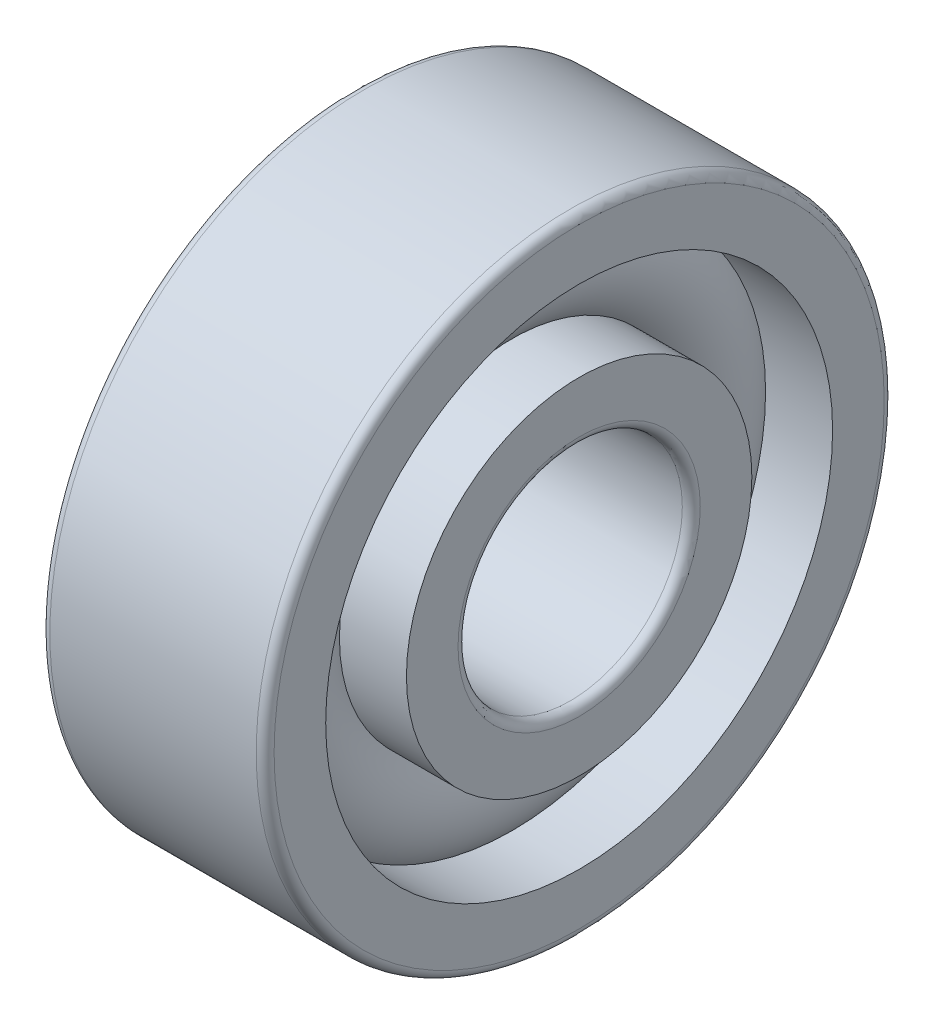
SolidWorks part; units mm, degrees
ref_plane "Plane1" through (0, 0, 0) normal (0, 0, 1) x (1, 0, 0)
ref_plane "Plane2" through (0, 0, 0) normal (0, 1, 0) x (1, 0, 0)
ref_plane "Plane3" through (0, 0, 0) normal (1, 0, 0) x (0, 0, -1)
sketch "Clipboard" plane through (0, 0, 0) normal (0, 0, 1) x (1, 0, 0)
  line L0 (-10, 0) -> (10, 0) construction
  line L1 (0, 0) -> (22.3471, -0.7804)
  line L2 (0, 0) -> (4.7471, 0.1658)
  line L3 (0, 0) -> (22.3471, -0.7804)
  line L4 (0, 0) -> (-22.3573, -0.3902)
  dimension "BallCLRad" = 4.75
sketch "CagSpiSke" plane through (0, 0, 0) normal (0, 0, 1) x (1, 0, 0)
  line L0 (0.135, 4.525) -> (0.135, 4.975)
  line L1 (0.135, 4.975) -> (-0.135, 4.975)
  line L2 (-0.135, 4.975) -> (-0.135, 4.525)
  line L3 (-0.135, 4.525) -> (0.135, 4.525)
  line L4 (-20.6375, 0) -> (20.6375, 0) construction
  line L5 (0, 0) -> (0, 23.7692) construction
  dimension "OD" = 9.95
  dimension "ID" = 9.05
revolve "CageSpine" add sketch "CagSpiSke" angle 0.001 about L4 reverse direction yes
ref_axis "Axis1" through (-50, 0, 0) along (1, 0, 0)
sketch "CagBalSke" plane through (0, 0, 0) normal (0, 0, 1) x (1, 0, 0)
  line L0 (-1.485, 4.75) -> (1.485, 4.75)
  line L1 (-1.905, 4.75) -> (1.905, 4.75) construction
  line L2 (-10, 0) -> (10, 0) construction
  line L3 (0, 0) -> (0, 24) construction
  arc A0 (1.485, 4.75) -> (-1.485, 4.75) centre (0, 4.75) cw
  dimension "BallCLRad" = 4.75
revolve "CageBall" [suppressed] add sketch "CagBalSke" angle 360 about L1 reverse direction yes
pattern_circular "CageBalls" [suppressed] count 2 every 180 about axis through (-50, 0, 0) along (1, 0, 0)
sketch "CagTrmODSke" plane through (0, 0, 0) normal (0, 0, 1) x (1, 0, 0)
  line L0 (1.486, 4.975) -> (1.486, 6.236)
  line L1 (1.486, 6.236) -> (-1.486, 6.236)
  line L2 (-1.486, 6.236) -> (-1.486, 4.975)
  line L3 (-1.486, 4.975) -> (1.486, 4.975)
  line L4 (-20.6375, 0) -> (20.6375, 0) construction
  line L5 (0, 0) -> (0, 25) construction
  dimension "Width" = 2.972
  dimension "ID" = 9.95
  dimension "OD" = 12.472
revolve "CageTrimOD" [suppressed] cut sketch "CagTrmODSke" angle 360 about L4 reverse direction yes
sketch "CagTrmIDSke" plane through (0, 0, 0) normal (0, 0, 1) x (1, 0, 0)
  line L0 (1.486, 3.266) -> (1.486, 4.525)
  line L1 (1.486, 4.525) -> (-1.486, 4.525)
  line L2 (-1.486, 4.525) -> (-1.486, 3.266)
  line L3 (-1.486, 3.266) -> (1.486, 3.266)
  line L4 (-20.6375, 0) -> (20.6375, 0) construction
  line L5 (0, 0) -> (0, 25) construction
  dimension "Width" = 2.972
  dimension "ID" = 6.532
  dimension "OD" = 9.05
revolve "CageTrimID" [suppressed] cut sketch "CagTrmIDSke" angle 360 about L4 reverse direction yes
sketch "BalSimSke" plane through (0, 0, 0) normal (0, 0, 1) x (1, 0, 0)
  line L0 (-10, 0) -> (10, 0) construction
  line L1 (-10, 4.75) -> (10, 4.75) construction
  line L2 (0, 0) -> (0, 23) construction
  circle A0 centre (0, 4.75) radius 1.35
  dimension "BallCLRad" = 4.75
  dimension "Ball_diameter" = 2.7
revolve "BallsSimplified" add sketch "BalSimSke" angle 360 about L0
sketch "BalDetSke" plane through (0, 0, 0) normal (0, 0, 1) x (1, 0, 0)
  line L0 (-1.35, 4.75) -> (1.35, 4.75)
  line L1 (-1.905, 4.75) -> (1.905, 4.75) construction
  line L2 (0, 0) -> (0, 25) construction
  arc A0 (1.35, 4.75) -> (-1.35, 4.75) centre (0, 4.75) cw
  dimension "BallCLRad" = 4.75
  dimension "Ball_diameter" = 2.7
revolve "BallDetailed" [suppressed] add sketch "BalDetSke" angle 360 about L1 reverse direction yes
sketch "InnRacSke" plane through (0, 0, 0) normal (0, 0, 1) x (1, 0, 0)
  line L0 (-0.9724, 3.85) -> (-2.5, 3.85)
  line L1 (-2.5, 3.85) -> (-2.5, 2.7)
  line L2 (-2.3, 2.5) -> (2.3, 2.5)
  line L3 (2.5, 2.7) -> (2.5, 3.85)
  line L4 (2.5, 3.85) -> (0.9724, 3.85)
  line L5 (-20.6375, 0) -> (20.6375, 0) construction
  line L6 (0, 0) -> (0, 30) construction
  arc A0 (-2.5, 2.7) -> (-2.3, 2.5) centre (-2.3, 2.7) ccw
  arc A1 (2.3, 2.5) -> (2.5, 2.7) centre (2.3, 2.7) ccw
  arc A2 (0.9724, 3.85) -> (-0.9724, 3.85) centre (0, 4.75) cw
  dimension "BallCLRad" = 4.75
  dimension "Fillet_radius" = 0.2
  dimension "Ball_diameter" = 2.65
  dimension "ID" = 5
  dimension "OD" = 7.7
  dimension "Width" = 5
revolve "InnerRace" add sketch "InnRacSke" angle 360 about L5 reverse direction yes
sketch "OutRacSke" plane through (0, 0, 0) normal (0, 0, 1) x (1, 0, 0)
  line L0 (-0.9724, 5.65) -> (-2.5, 5.65)
  line L1 (-2.5, 5.65) -> (-2.5, 6.8)
  line L2 (-2.3, 7) -> (2.3, 7)
  line L3 (2.5, 6.8) -> (2.5, 5.65)
  line L4 (2.5, 5.65) -> (0.9724, 5.65)
  line L5 (-20.6375, 0) -> (20.6375, 0) construction
  line L6 (0, 0) -> (0, 30) construction
  arc A0 (-2.5, 6.8) -> (-2.3, 7) centre (-2.3, 6.8) cw
  arc A1 (2.3, 7) -> (2.5, 6.8) centre (2.3, 6.8) cw
  arc A2 (0.9724, 5.65) -> (-0.9724, 5.65) centre (0, 4.75) ccw
  dimension "BallCLRad" = 4.75
  dimension "Fillet_radius" = 0.2
  dimension "Ball_diameter" = 2.65
  dimension "Width" = 5
revolve "OuterRace" add sketch "OutRacSke" angle 360 about L5 reverse direction yes
pattern_circular "BallsDetailed" [suppressed] count 2 every 180 about axis through (-50, 0, 0) along (1, 0, 0)
equation "\"BallCLRad@Clipboard\" = ( \"OD@OutRacSke\" + \"ID@InnRacSke\" ) / 4"
equation "\"BallCLRad@BalSimSke\" = \"BallCLRad@Clipboard\""
equation "\"BallCLRad@BalDetSke\" = \"BallCLRad@Clipboard\""
equation "\"BallCLRad@InnRacSke\" = \"BallCLRad@Clipboard\""
equation "\"BallCLRad@OutRacSke\" = \"BallCLRad@Clipboard\""
equation "\"Ball_diameter@InnRacSke\" = \"Ball_diameter@BalDetSke\" - 0.05"
equation "\"Ball_diameter@OutRacSke\" = \"Ball_diameter@BalDetSke\" - 0.05"
equation "\"Ball_diameter@BalSimSke\" = \"Ball_diameter@BalDetSke\""
equation "\"Width@OutRacSke\" = \"Width@InnRacSke\""
equation "\"Fillet_radius@OutRacSke\" = \"Fillet_radius@InnRacSke\""
equation "\"Max_count@Clipboard\" = int( 3.14159265 / atn(( \"Ball_diameter@BalDetSke\" / 2) / sqr( \"BallCLRad@Clipboard\"  *  \"BallCLRad@Clipboard\" - ( \"Ball_diameter@BalDetSke\" / 2) *  ( \"Ball_diameter@BalDetSke\" / 2))))"
equation "\"Max_count@Clipboard\" = ((sgn( \"Max_count@Clipboard\" - \"Count@Clipboard\" )-1)*( \"Max_count@Clipboard\" - \"Count@Clipboard\" ))/-2+ \"Count@Clipboard\""
equation "\"Count@BallsDetailed\" = int( \"Show_count@Clipboard\" ) "
equation "\"Count@BallsDetailed\" = ((sgn( \"Count@BallsDetailed\" - \"Max_count@Clipboard\" )-1)*( \"Count@BallsDetailed\" - \"Max_count@Clipboard\" ))/-2+ \"Max_count@Clipboard\""
equation "\"Count@BallsDetailed\" = ((sgn( \"Count@BallsDetailed\" - \"Min_count@Clipboard\" )+1)*( \"Count@BallsDetailed\" - \"Min_count@Clipboard\"))/2 +\"Min_count@Clipboard\""
equation "\"Angle@BallsDetailed\" = 360.0 / \"Max_count@Clipboard\""
equation "\"BallCLRad@CagBalSke\" = \"BallCLRad@Clipboard\""
equation "\"Count@CageBalls\" = \"Count@BallsDetailed\""
equation "\"Angle@CageBalls\" = \"Angle@BallsDetailed\""
equation "\"Angle@CageSpine\" =  \"Angle@CageBalls\" * ( \"Count@CageBalls\" -1 + int( \"Count@CageBalls\" / \"Max_count@Clipboard\" ) )  + 0.001 -  int( \"Count@CageBalls\" / \"Max_count@Clipboard\" ) * 0.001"
equation "\"Angle@CageSpine\" =  \"Angle@CageSpine\" * int( \"Min_count@Clipboard\" / 2) + int(1 / \"Min_count@Clipboard\")  * 0.001"
equation "\"CageWallOD@CagBalSke\" =  \"Ball_diameter@BalDetSke\" * 1.1"
equation "\"Thickness@CagSpiSke\" =  \"Ball_diameter@BalDetSke\" * 0.1"
equation "\"OD@CagTrmODSke\" = \"BallCLRad@Clipboard\" * 2 + \"CageWallOD@CagBalSke\" + 0.002"
equation "\"ID@CagTrmODSke\" = \"BallCLRad@Clipboard\" * 2 + \"Ball_diameter@BalDetSke\" / 6"
equation "\"OD@CagTrmIDSke\" = \"BallCLRad@Clipboard\" * 2 - \"Ball_diameter@BalDetSke\" / 6"
equation "\"ID@CagTrmIDSke\" = \"BallCLRad@Clipboard\" * 2 - \"CageWallOD@CagBalSke\" + 0.002"
equation "\"OD@CagSpiSke\" = \"ID@CagTrmODSke\""
equation "\"ID@CagSpiSke\" = \"OD@CagTrmIDSke\""
equation "\"Width@CagTrmODSke\" = \"CageWallOD@CagBalSke\" + 0.002"
equation "\"Width@CagTrmIDSke\" = \"CageWallOD@CagBalSke\" + 0.002"
